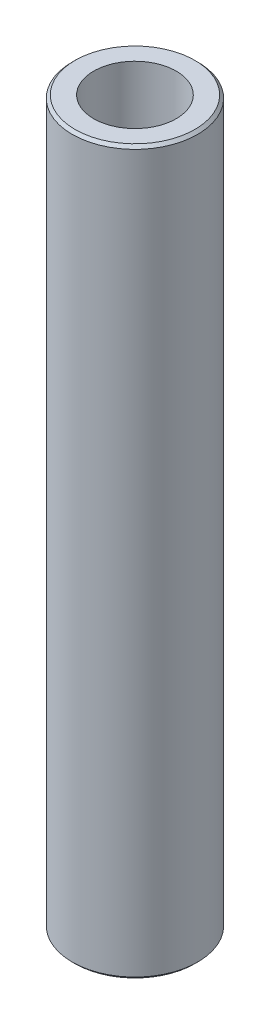
SolidWorks part; units mm, degrees
ref_plane "Front Plane" through (0, 0, 0) normal (0, 0, 1) x (1, 0, 0)
ref_plane "Top Plane" through (0, 0, 0) normal (0, 1, 0) x (1, 0, 0)
ref_plane "Right Plane" through (0, 0, 0) normal (1, 0, 0) x (0, 0, -1)
sketch "Sketch1" plane through (0, 0, 0) normal (0, 1, 0) x (1, 0, 0)
  circle A0 centre (0, 0) radius 15
  dimension "SHAFT_OD" = 30
extrude "Boss-Extrude1" add sketch "Sketch1" along normal blind 172.7435
sketch "Sketch2" plane through (0, 0, 0) normal (0, 1, 0) x (1, 0, 0)
  circle A0 centre (0, 0) radius 9.8703
  dimension "BORE_D" = 19.7405
extrude "Cut-Extrude1" cut sketch "Sketch2" along normal through all
chamfer "Chamfer1" distance 0.6764 angle 45 2 edges at (0, 172.7435, 15) (0, 0, 15)
